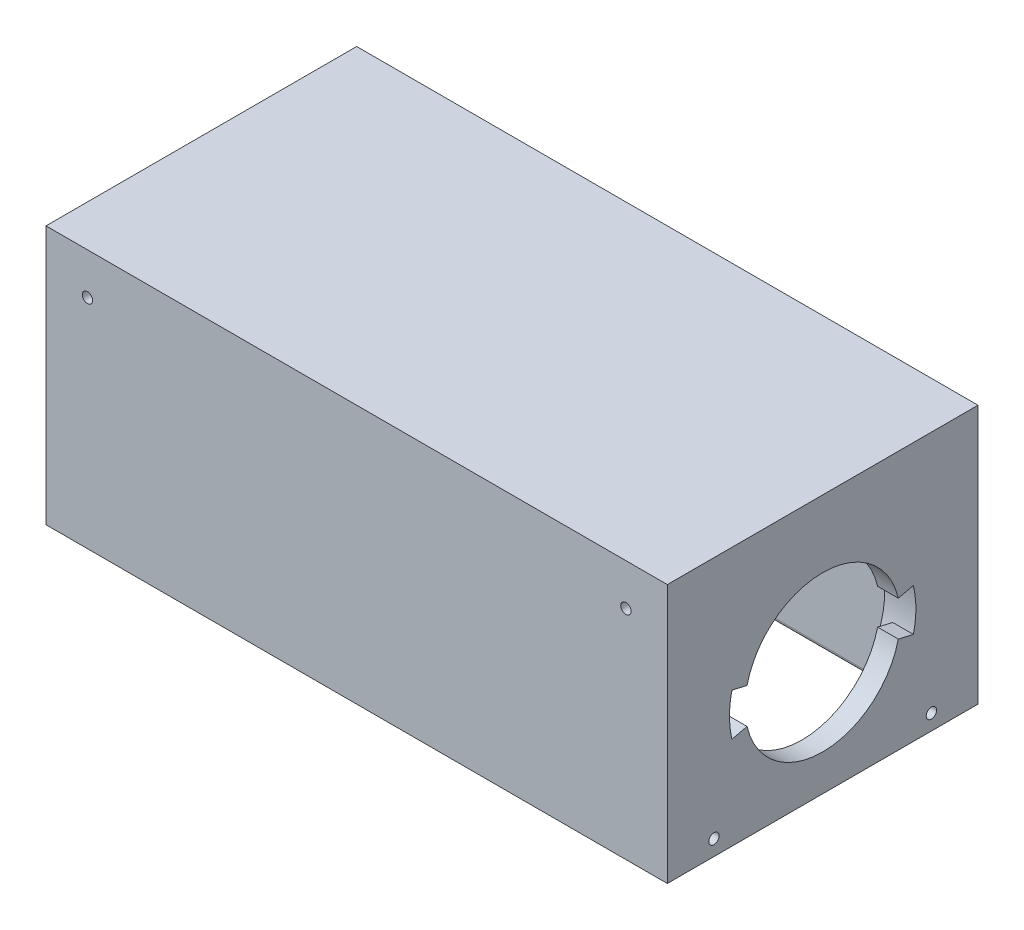
SolidWorks part; units mm, degrees
material "ABS PC"
ref_plane "Front Plane" through (0, 0, 0) normal (0, 0, 1) x (1, 0, 0)
ref_plane "Top Plane" through (0, 0, 0) normal (0, 1, 0) x (1, 0, 0)
ref_plane "Right Plane" through (0, 0, 0) normal (1, 0, 0) x (0, 0, -1)
sketch "Sketch1" plane through (0, 0, 0) normal (0, 1, 0) x (1, 0, 0)
  line L1 (150, -75) -> (-150, -75)
  line L2 (150, -75) -> (150, 75)
  line L3 (150, 75) -> (-150, 75)
  line L4 (-150, -75) -> (-150, 75)
  line L5 (150, -75) -> (-150, 75) construction
  line L6 (150, 75) -> (-150, -75) construction
  point P0 (0, 0)
  dimension "D1" = 300
  dimension "D2" = 150
extrude "Boss-Extrude1" add sketch "Sketch1" along normal blind 125
sketch "Sketch2" plane through (0, 0, 0) normal (0, -1, 0) x (1, 0, 0)
  line L0 (-150, 75) -> (150, 75) construction
  line L1 (135, -60) -> (-135, -60)
  line L2 (135, -60) -> (135, 60)
  line L3 (135, 60) -> (-135, 60)
  line L4 (-135, -60) -> (-135, 60)
  line L5 (135, -60) -> (-135, 60) construction
  line L6 (135, 60) -> (-135, -60) construction
  line L7 (150, 75) -> (150, -75) construction
  point P0 (0, 0)
  point P8 (150, 0)
  dimension "D1" = 15
  dimension "D2" = 15
extrude "Cut-Extrude1" cut sketch "Sketch2" against normal blind 110
sketch "Sketch4" plane through (150, 0, 0) normal (1, 0, 0) x (0, 0, -1)
  line L0 (-75, 0) -> (75, 0) construction
  line L1 (75, 125) -> (75, 0) construction
  line L5 (-75, 125) -> (-75, 0) construction
  circle A0 centre (-52.5, 7.5) radius 2.5
  circle A1 centre (52.5, 7.5) radius 2.5
  dimension "D3" = 5
  dimension "D4" = 5
  dimension "D1" = 7.5
  dimension "D2" = 22.5
  dimension "D5" = 7.5
  dimension "D6" = 22.5
extrude "Cut-Extrude5" cut sketch "Sketch4" against normal blind 350
sketch "Sketch6" plane through (0, 0, 75) normal (0, 0, 1) x (1, 0, 0)
  line L0 (-150, 125) -> (-150, 0) construction
  line L1 (-150, 125) -> (150, 125) construction
  line L2 (0, 140.9499) -> (0, -14.4188) construction
  circle A0 centre (-130, 105) radius 2.5
  circle A1 centre (130, 105) radius 2.5
  dimension "D1" = 5
  dimension "D2" = 20
  dimension "D3" = 20
extrude "Cut-Extrude6" cut sketch "Sketch6" against normal blind 175
fillet "Fillet1" radius 5 1 edges at (0, 110, -60)
fillet "Fillet2" radius 5 1 edges at (0, 110, 60)
fillet "Fillet3" radius 5 5 edges at (-135, 52.5, 60) (-135, 108.5355, 58.5355) (-135, 52.5, -60) (-135, 108.5355, -58.5355) (-135, 110, 0)
fillet "Fillet4" radius 5 5 edges at (135, 52.5, -60) (135, 108.5355, -58.5355) (135, 52.5, 60) (135, 108.5355, 58.5355) (135, 110, 0)
fillet "Fillet5" radius 2 8 edges at (-133.5355, 0, -58.5355) (-135, 0, 0) (-133.5355, 0, 58.5355) (0, 0, 60) (133.5355, 0, 58.5355) (135, 0, 0) (133.5355, 0, -58.5355) (0, 0, -60)
sketch "Sketch7" plane through (150, 0, 0) normal (1, 0, 0) x (0, 0, -1)
  line L0 (-75, 0) -> (75, 0) construction
  circle A0 centre (0, 55) radius 37.5
  dimension "D1" = 75
  dimension "D2" = 55
extrude "Cut-Extrude7" cut sketch "Sketch7" against normal blind 25
sketch "Sketch8" plane through (135, 0, 0) normal (-1, 0, 0) x (0, 0, 1)
  circle A0 centre (0, 55) radius 45
  dimension "D1" = 90
extrude "Cut-Extrude8" cut sketch "Sketch8" against normal blind 5
sketch "Sketch9" plane through (150, 0, 0) normal (1, 0, 0) x (0, 0, -1)
  line L0 (0, 141.2164) -> (0, -8.4534) construction
  line L1 (0, 55) -> (43.8171, 65.25)
  line L2 (43.8171, 44.75) -> (0, 55)
  line L3 (0, 55) -> (-43.8171, 65.25)
  line L4 (-43.8171, 44.75) -> (0, 55)
  arc A0 (43.8171, 65.25) -> (43.8171, 44.75) centre (0, 55) cw
  circle A1 centre (0, 55) radius 45 construction
  arc A2 (-43.8171, 65.25) -> (-43.8171, 44.75) centre (0, 55) ccw
  circle M3 centre (0, 55) radius 37.5
  dimension "D1" = 10.25
  dimension "D2" = 10.25
extrude "Cut-Extrude9" cut sketch "Sketch9" against normal blind 20 contours L3 A2 L4 M3 | A0 L1 L2 M3 region at (150, 55, -41.0006) region at (150, 55, 41.0006)
sketch "Sketch10" plane through (140, 0, 0) normal (-1, 0, 0) x (0, 0, 1)
  line L0 (-3.5, 99.8637) -> (-3.5, 92.3363)
  line L1 (3.5, 92.3363) -> (3.5, 99.8637)
  arc A0 (3.5, 99.8637) -> (-3.5, 99.8637) centre (0, 55) ccw
  circle A1 centre (0, 55) radius 45 construction
  arc A2 (3.5, 92.3363) -> (-3.5, 92.3363) centre (0, 55) ccw
  arc A3 (36.5142, 63.5417) -> (-36.5142, 63.5417) centre (0, 55) ccw construction
  dimension "D1" = 3.5
  dimension "D2" = 3.5
  dimension "D3" = 3.5
  dimension "D4" = 3.5
extrude "Boss-Extrude2" add sketch "Sketch10" along normal blind 5
